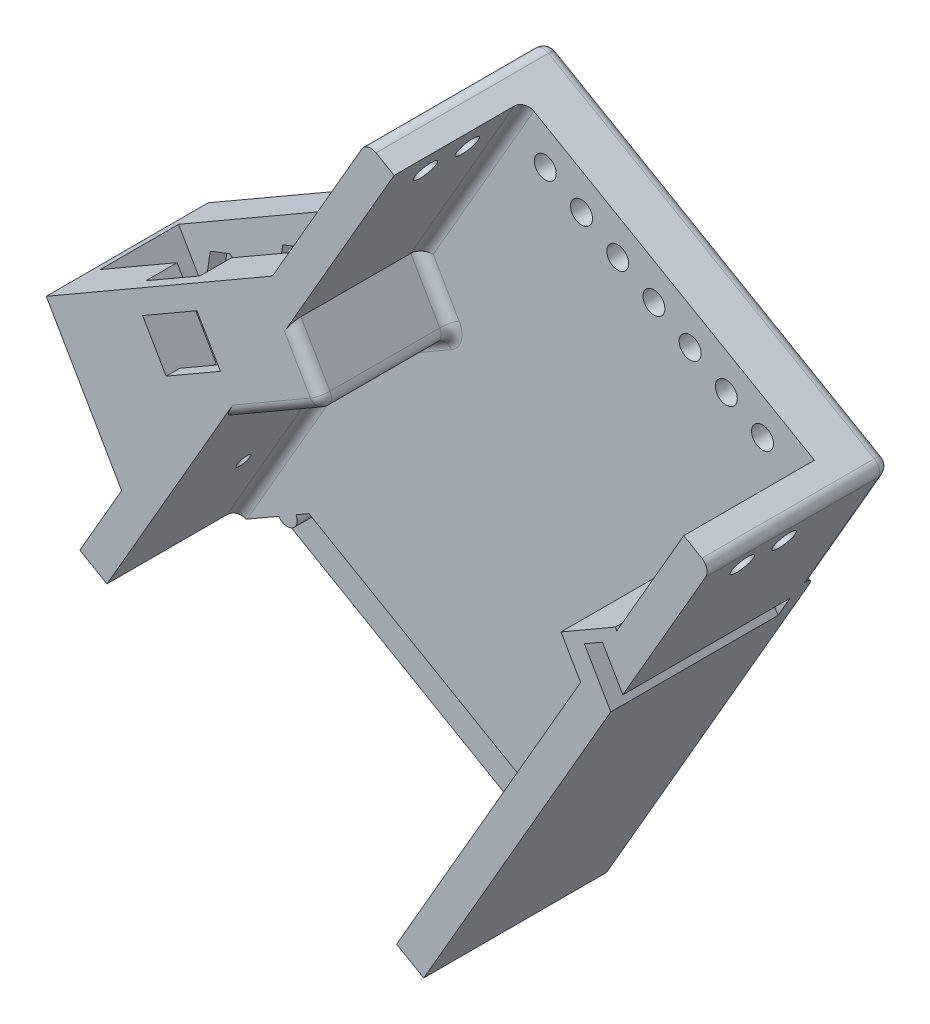
SolidWorks part; units mm, degrees
material "ABS"
ref_plane "前基準面" through (0, 0, 0) normal (0, 0, 1) x (1, 0, 0)
ref_plane "上基準面" through (0, 0, 0) normal (0, 1, 0) x (1, 0, 0)
ref_plane "右基準面" through (0, 0, 0) normal (1, 0, 0) x (0, 0, -1)
sketch "草圖2" plane through (0, 0, 0) normal (0, 0, 1) x (1, 0, 0)
  line L1 (-42.4346, 62.0442) -> (67.4854, 62.0442)
  line L2 (-42.4346, 62.0442) -> (-42.4346, -13.9558)
  line L3 (-42.4346, -13.9558) -> (67.4854, -13.9558)
  line L4 (67.4854, 62.0442) -> (67.4854, -13.9558)
  dimension "D1" = 109.92
  dimension "D2" = 76
extrude "填料-伸長1" add sketch "草圖2" along normal blind 10
sketch "草圖3" plane through (0, 0, 10) normal (0, 0, 1) x (1, 0, 0)
  line L0 (67.4854, 54.1442) -> (67.4854, -6.0558)
  line L1 (67.4854, -13.9558) -> (67.4854, 62.0442) construction
  line L2 (67.4854, 62.0442) -> (-42.4346, 62.0442) construction
  line L3 (67.4854, 54.1442) -> (55.4854, 47.2142)
  line L4 (55.4854, 47.2142) -> (55.4854, 0.8742)
  line L5 (55.4854, 0.8742) -> (67.4854, -6.0558)
  circle A0 centre (59.5654, 49.6442) radius 1.9
  circle A1 centre (59.5654, -1.5558) radius 1.9
  line M6 (67.4854, -13.9558) -> (67.4854, 62.0442)
  dimension "D7" = 7.92
  dimension "D8" = 7.92
  dimension "D9" = 3.8
  dimension "D10" = 3.8
  dimension "D12" = 12.4
  dimension "D1" = 60.2
  dimension "D2" = 7.9
  dimension "D3" = 12
  dimension "D4" = 12
  dimension "D5" = 46.34
  dimension "D6" = 6.93
  dimension "D11" = 51.2
extrude "除料-伸長1" cut sketch "草圖3" against normal blind 5 contours A1 L5 L3 A0 L4 M6
sketch "草圖4" plane through (0, 0, 5) normal (0, 0, 1) x (1, 0, 0)
  line L0 (67.4854, -6.0558) -> (67.4854, 54.1442) construction
  circle A0 centre (59.5654, 41.6442) radius 2
  circle A2 centre (59.5654, 33.6442) radius 2
  circle A3 centre (59.5654, 6.4442) radius 2
  circle A5 centre (59.5654, 14.4442) radius 2
  arc A6 (57.953, -0.5508) -> (61.2418, -2.4501) centre (59.5654, -1.5558) ccw construction
  dimension "D1" = 7.92
  dimension "D2" = 7.92
  dimension "D3" = 4
  dimension "D5" = 4
  dimension "D7" = 8
  dimension "D8" = 2
extrude "除料-伸長2" cut sketch "草圖4" against normal through all
sketch "草圖5" plane through (0, 0, 10) normal (0, 0, 1) x (1, 0, 0)
  line L0 (67.4854, -13.9558) -> (67.4854, -6.0558) construction
  line L1 (-42.4346, -13.9558) -> (67.4854, -13.9558)
  line L2 (-42.4346, -13.9558) -> (-42.4346, -7.9558)
  line L3 (-42.4346, -7.9558) -> (67.4854, -7.9558)
  line L4 (67.4854, -13.9558) -> (67.4854, -7.9558)
  line L5 (-42.4346, 62.0442) -> (-42.4346, -13.9558) construction
  line L6 (67.4854, 62.0442) -> (-42.4346, 62.0442)
  line L7 (67.4854, 62.0442) -> (67.4854, 56.0442)
  line L8 (67.4854, 56.0442) -> (-42.4346, 56.0442)
  line L9 (-42.4346, 62.0442) -> (-42.4346, 56.0442)
  dimension "D1" = 6
  dimension "D2" = 6
extrude "填料-伸長2" add sketch "草圖5" along normal blind 25
sketch "草圖7" plane through (0, -7.9558, 0) normal (0, 1, 0) x (1, 0, 0)
  line L0 (67.4854, -10) -> (-42.4346, -10) construction
  line L1 (-42.4346, -35) -> (-42.4346, -10) construction
  circle A0 centre (-36.4346, -18) radius 2.1
  circle A1 centre (-36.4346, -26) radius 2.1
  dimension "D1" = 4.2
  dimension "D2" = 8
  dimension "D4" = 6
  dimension "D3" = 2
extrude "除料-伸長3" cut sketch "草圖7" against normal through all both and the other way through all
sketch "草圖9" plane through (0, 0, 10) normal (0, 0, 1) x (1, 0, 0)
  line L2 (-42.4346, 56.0442) -> (-42.4346, -7.9558) construction
  line L3 (67.4854, -7.9558) -> (-42.4346, -7.9558) construction
  circle A0 centre (-36.4346, 0.0442) radius 2.1
  circle A1 centre (-36.4346, 8.0442) radius 2.1
  circle A2 centre (-36.4346, 16.0442) radius 2.1
  circle A3 centre (-36.4346, 24.0442) radius 2.1
  circle A4 centre (-36.4346, 32.0442) radius 2.1
  circle A5 centre (-36.4346, 40.0442) radius 2.1
  circle A6 centre (-36.4346, 48.0442) radius 2.1
  dimension "D1" = 6
  dimension "D2" = 4.2
  dimension "D3" = 8
  dimension "D4" = 7
extrude "除料-伸長4" cut sketch "草圖9" against normal through all
sketch "草圖10" plane through (0, 0, 0) normal (0, 0, -1) x (-1, 0, 0)
  line L0 (36.4346, 0.0442) -> (36.4346, 48.0442) construction
  line L1 (32.4346, 0.0442) -> (32.4346, 48.0442)
  line L2 (40.4346, 0.0442) -> (40.4346, 48.0442)
  arc A0 (32.4346, 0.0442) -> (40.4346, 0.0442) centre (36.4346, 0.0442) ccw
  arc A1 (40.4346, 48.0442) -> (32.4346, 48.0442) centre (36.4346, 48.0442) ccw
  point P4 (36.4346, 24.0442)
  dimension "D1" = 8
extrude "除料-伸長5" cut sketch "草圖10" against normal blind 5
sketch "草圖11" plane through (0, 0, 35) normal (0, 0, 1) x (1, 0, 0)
  line L0 (51.4854, 62.0442) -> (37.0517, 87.0442)
  line L1 (67.4854, 62.0442) -> (-42.4346, 62.0442) construction
  line L2 (37.0517, 87.0442) -> (-6.2496, 62.0442)
  line L3 (-6.2496, 62.0442) -> (51.4854, 62.0442)
  line L4 (67.4854, 56.0442) -> (67.4854, 62.0442) construction
  dimension "D1" = 30
  dimension "D2" = 270
  dimension "D3" = 50
  dimension "D4" = 16
extrude "填料-伸長3" add sketch "草圖11" along direction (0, 0, 1) on the side against the normal through all
sketch "草圖12" plane through (0, 0, 35) normal (0, 0, 1) x (1, 0, 0)
  line L0 (-6.2496, 62.0442) -> (37.0517, 87.0442)
  line L1 (-6.2496, 62.0442) -> (3.7504, 44.7237)
  line L2 (37.0517, 87.0442) -> (47.0517, 69.7237)
  line L3 (3.7504, 44.7237) -> (47.0517, 69.7237)
  dimension "D1" = 20
extrude "填料-伸長4" add sketch "草圖12" along direction (0, 0, 1) on the side against the normal up to next (35 mm away)
sketch "草圖13" plane through (-28.4283, 49.2393, 0) normal (-0.5, 0.866, 0) x (0.866, 0.5, 0)
  line L1 (73.6098, -26.4) -> (27.6098, -26.4)
  line L2 (73.6098, -26.4) -> (73.6098, -11.4)
  line L3 (73.6098, -11.4) -> (27.6098, -11.4)
  line L4 (27.6098, -26.4) -> (27.6098, -11.4)
  line L6 (75.6098, 0) -> (75.6098, -35) construction
  line L8 (56.6098, -26.4) -> (44.6098, -26.4)
  line L9 (56.6098, -26.4) -> (56.6098, -32.4)
  line L10 (56.6098, -32.4) -> (44.6098, -32.4)
  line L11 (44.6098, -26.4) -> (44.6098, -32.4)
  dimension "D1" = 15
  dimension "D2" = 12.5
  dimension "D3" = 46
  dimension "D4" = 2
  dimension "D5" = 12
  dimension "D6" = 17
  dimension "D7" = 21
extrude "除料-伸長6" cut sketch "草圖13" against normal blind 15 contours L4 L1 L2 L3 | L1 L11 L10 L9
sketch "草圖14" plane through (0, 0, 32.4) normal (0, 0, -1) x (-1, 0, 0)
  line L4 (-22.5972, 74.0801) -> (-27.0972, 66.2858)
  line L5 (-22.5972, 74.0801) -> (-12.2049, 68.0801)
  line L6 (-27.0972, 66.2858) -> (-16.7049, 60.2858)
  line L7 (-12.2049, 68.0801) -> (-16.7049, 60.2858)
  line L8 (-28.0972, 64.5538) -> (-20.5972, 77.5442) construction
  line L10 (-28.0972, 64.5538) -> (-17.7049, 58.5538) construction
  line L11 (-17.7049, 58.5538) -> (-10.2049, 71.5442) construction
  dimension "D1" = 2
  dimension "D2" = 0
  dimension "D3" = 9
extrude "除料-伸長7" cut sketch "草圖14" against normal blind 15
sketch "草圖15" plane through (-20.9283, 36.2489, 0) normal (-0.5, 0.866, 0) x (0.866, 0.5, 0)
  line L2 (27.6098, -26.4) -> (27.6098, -11.4) construction
  line L4 (73.6098, -11.4) -> (27.6098, -11.4) construction
  circle A0 centre (69.1098, -18.9) radius 1.25
  circle A1 centre (32.1098, -18.9) radius 1.25
  dimension "D1" = 37
  dimension "D2" = 4.5
  dimension "D3" = 7.5
  dimension "D4" = 2.5
  dimension "D5" = 2.5
  dimension "D6" = 7.5
extrude "除料-伸長8" cut sketch "草圖15" along direction (0.5, -0.866, 0) on the side against the normal up to next (28.7095 mm away)
sketch "草圖18" plane through (0, 0, 35) normal (0, 0, 1) x (1, 0, 0)
  line L0 (-13.3436, -13.9558) -> (-13.5936, -13.5228)
  line L1 (-42.4346, -13.9558) -> (67.4854, -13.9558) construction
  line L2 (-13.5936, -13.5228) -> (-10.1295, -11.5228)
  line L3 (-10.1295, -11.5228) -> (-8.7248, -13.9558)
  line L4 (-8.7248, -13.9558) -> (-13.3436, -13.9558)
  line L5 (-4.106, -13.9558) -> (-6.6654, -9.5228)
  line L6 (-6.6654, -9.5228) -> (-3.2013, -7.5228)
  line L7 (-3.2013, -7.5228) -> (0.5128, -13.9558)
  line L8 (0.5128, -13.9558) -> (-4.106, -13.9558)
  line L9 (-13.5936, -13.5228) -> (-3.2013, -7.5228)
  line L10 (-13.5936, -13.5228) -> (-17.0936, -7.4606)
  line L11 (-3.2013, -7.5228) -> (-6.7013, -1.4606)
  line L12 (-17.0936, -7.4606) -> (-6.7013, -1.4606)
  line M9 (67.4854, -7.9558) -> (-42.4346, -7.9558)
  line M13 (-42.4346, -13.9558) -> (67.4854, -13.9558)
  dimension "D1" = 60
  dimension "D2" = 70
  dimension "D3" = 4
  dimension "D4" = 0.5
  dimension "D5" = 60
  dimension "D6" = 4
  dimension "D7" = 0
  dimension "D8" = 4
  dimension "D9" = 7
extrude "填料-伸長5" add sketch "草圖18" against normal up to surface (35 mm away) contours L7 L6 M13 | L2 L3 L0 M13 | L5 L6 M13 | L12 L10 L6 L11 M13 M9 | L12 L11 M9
sketch "草圖21" plane through (0, 0, 0) normal (0, 0, -1) x (-1, 0, 0)
  line L1 (-37.0517, 87.0442) -> (-43.0517, 76.6519)
  line L5 (-43.0517, 76.6519) -> (-51.4854, 62.0442)
  line L6 (-51.4854, 62.0442) -> (-17.7504, 62.0442)
  line L8 (-17.7504, 62.0442) -> (-11.7504, 72.4365)
  line L9 (-37.0517, 87.0442) -> (6.2496, 62.0442) construction
  line L10 (-11.7504, 72.4365) -> (-37.0517, 87.0442)
  line L11 (6.2496, 62.0442) -> (-17.7504, 62.0442)
  dimension "D1" = 12
  dimension "D2" = 180
extrude "除料-伸長10" cut sketch "草圖21" against normal blind 4
sketch "草圖22" plane through (0, 0, 4) normal (0, 0, -1) x (-1, 0, 0)
  line L2 (-37.0517, 87.0442) -> (-51.4854, 62.0442) construction
  line L3 (-11.7504, 72.4365) -> (-37.0517, 87.0442) construction
  circle A0 centre (-34.1235, 76.116) radius 2
  circle A1 centre (-20.2671, 68.116) radius 2
  dimension "D1" = 8
  dimension "D2" = 2
  dimension "D3" = 4
  dimension "D4" = 8
extrude "除料-伸長11" cut sketch "草圖22" against normal up to next
sketch "草圖23" plane through (0, 0, 11.4) normal (0, 0, 1) x (1, 0, 0)
  line L0 (16.5396, 69.5671) -> (17.1466, 65.6134)
  line L1 (30.396, 77.5671) -> (31.003, 73.6134)
  line L2 (31.003, 73.6134) -> (34.7305, 72.1623)
  line L3 (34.7305, 72.1623) -> (37.851, 74.6648)
  line L4 (37.851, 74.6648) -> (37.244, 78.6185)
  line L5 (37.244, 78.6185) -> (33.5165, 80.0696)
  line L6 (33.5165, 80.0696) -> (30.396, 77.5671)
  line L7 (17.1466, 65.6134) -> (20.8741, 64.1623)
  line L8 (20.8741, 64.1623) -> (23.9946, 66.6648)
  line L9 (23.9946, 66.6648) -> (23.3876, 70.6185)
  line L10 (23.3876, 70.6185) -> (19.6601, 72.0696)
  line L11 (19.6601, 72.0696) -> (16.5396, 69.5671)
  circle A0 centre (34.1235, 76.116) radius 4 construction
  circle A1 centre (20.2671, 68.116) radius 4 construction
  dimension "D1" = 8
  dimension "D2" = 2
extrude "除料-伸長12" cut sketch "草圖23" against normal blind 3.5
sketch "草圖24" plane through (0, 0, 35) normal (0, 0, 1) x (1, 0, 0)
  line L0 (-7.5701, -15.9558) -> (-4.106, -13.9558)
  line L1 (-7.5701, -15.9558) -> (-12.6295, -7.1927)
  line L2 (-4.106, -13.9558) -> (-9.1654, -5.1927)
  line L3 (-12.6295, -7.1927) -> (-9.1654, -5.1927)
  line L4 (-17.0936, -7.4606) -> (-6.7013, -1.4606) construction
  line L5 (-42.4346, -13.9558) -> (67.4854, -13.9558) construction
  line L7 (-16.8077, -7.9558) -> (-17.0936, -7.4606) construction
  dimension "D1" = 2
  dimension "D2" = 4
  dimension "D3" = 4
extrude "除料-伸長14" cut sketch "草圖24" against normal up to next
sketch "草圖25" plane through (0, 0, 0) normal (0, 0, -1) x (-1, 0, 0)
  line L0 (8.7248, -13.9558) -> (4.106, -13.9558)
  line L1 (4.106, -13.9558) -> (9.1654, -5.1927)
  line L2 (9.1654, -5.1927) -> (12.6295, -7.1927)
  line L3 (12.6295, -7.1927) -> (8.7248, -13.9558)
extrude "填料-伸長6" add sketch "草圖25" against normal blind 3
sketch "草圖27" plane through (0, 0, 35) normal (0, 0, 1) x (1, 0, 0)
  line L0 (-42.4346, -13.9558) -> (-8.7248, -13.9558) construction
  line L1 (-7.5792, -13.9558) -> (-12.106, -13.9558)
  line L2 (-7.5792, -13.9558) -> (-7.5792, -18.762)
  line L3 (-7.5792, -18.762) -> (-12.106, -18.762)
  line L4 (-12.106, -13.9558) -> (-12.106, -18.762)
  dimension "D1" = 8
extrude "填料-伸長7" add sketch "草圖27" against normal up to surface (35 mm away) up to face at (10.479, 41.8145, 0)
fillet "圓角1" radius 2 18 edges at (67.4854, 55.0942, 10) (-24.3421, 62.0442, 0) (-6.2496, 62.0442, 17.5) (45.4218, 56.0442, 10) (0.4825, 50.3839, 10) (13.5543, 50.3839, 10) (3.7504, 44.7237, 22.5) (0.4825, 50.3839, 35) (13.5543, 50.3839, 35) (2.7504, 67.2403, 0) (-12.106, -16.3589, 0) (67.4854, -7.0058, 10) (-27.2703, -13.9558, 0) (32.2671, -7.9558, 10) (-42.4346, 24.0442, 0) (-22.61, 56.0442, 10) (-42.4346, 62.0442, 17.5) (-42.4346, -13.9558, 17.5)
sketch "草圖28" plane through (0, 0, 35) normal (0, 0, 1) x (1, 0, 0)
  line L1 (-12.106, -13.9558) -> (-7.5792, -13.9558)
  line L2 (-12.106, -13.9558) -> (-12.106, -18.762)
  line L3 (-12.106, -18.762) -> (-7.5792, -18.762)
  line L4 (-7.5792, -13.9558) -> (-7.5792, -18.762)
extrude "除料-伸長15" cut sketch "草圖28" against normal up to next
mirror "鏡射1" about plane through (51.4854, 62.0442, 0) normal (0.866, 0.5, 0) of bodies 130 127
delete or keep bodies "本體-刪除/保留 1" type delete bodies bodies 130
